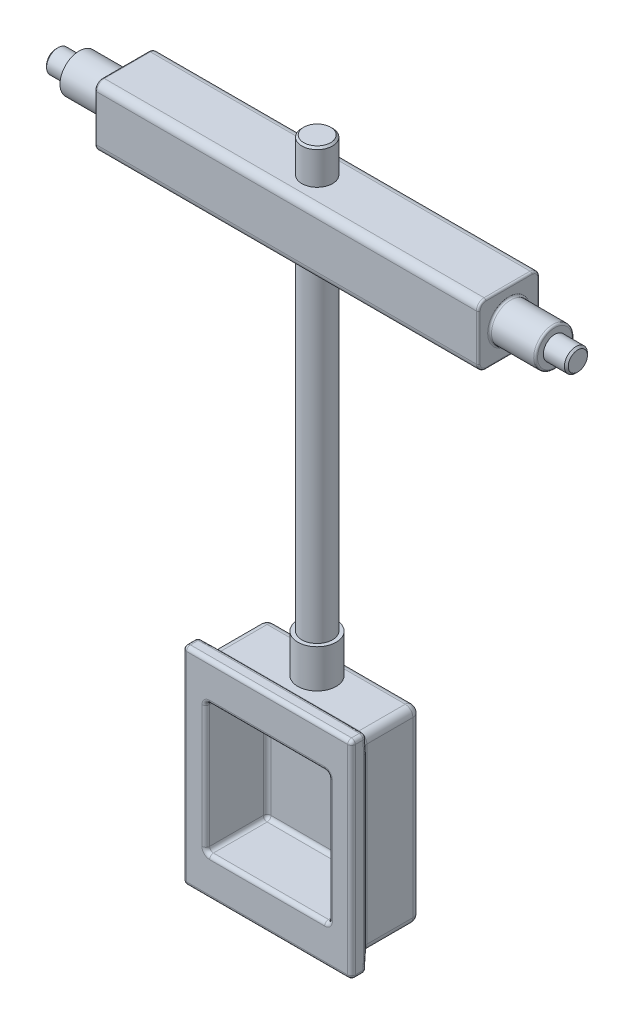
SolidWorks part; units mm, degrees
ref_plane "Front Plane" through (0, 0, 0) normal (0, 0, 1) x (1, 0, 0)
ref_plane "Top Plane" through (0, 0, 0) normal (0, 1, 0) x (1, 0, 0)
ref_plane "Right Plane" through (0, 0, 0) normal (1, 0, 0) x (0, 0, -1)
sketch "Sketch1" plane through (0, 0, 0) normal (0, 0, 1) x (1, 0, 0)
  line L1 (-10, -12.3) -> (10, -12.3)
  line L2 (-10, -12.3) -> (-10, 12.3)
  line L3 (-10, 12.3) -> (10, 12.3)
  line L4 (10, -12.3) -> (10, 12.3)
  line L5 (-10, -12.3) -> (10, 12.3) construction
  line L6 (-10, 12.3) -> (10, -12.3) construction
  line L7 (-8, -8.5) -> (8, -8.5)
  line L8 (-8, -8.5) -> (-8, 8.5)
  line L9 (-8, 8.5) -> (8, 8.5)
  line L10 (8, -8.5) -> (8, 8.5)
  line L11 (-8, -8.5) -> (8, 8.5) construction
  line L12 (-8, 8.5) -> (8, -8.5) construction
  line L13 (-11, -13.5) -> (11, -13.5)
  line L14 (-11, -13.5) -> (-11, 13.5)
  line L15 (-11, 13.5) -> (11, 13.5)
  line L16 (11, -13.5) -> (11, 13.5)
  line L17 (-11, -13.5) -> (11, 13.5) construction
  line L18 (-11, 13.5) -> (11, -13.5) construction
  point P0 (0, 0)
  point P6 (0, 0)
  point P11 (0, 0)
  point P16 (-9.0897, 12.4239)
  dimension "D1" = 17
  dimension "D2" = 16
  dimension "D3" = 22
  dimension "D4" = 27
  dimension "D5" = 1
  dimension "D6" = 1.2
extrude "Boss-Extrude1" add sketch "Sketch1" along normal blind 2 contours L13 L16 L15 L14 L4 L1 L2 L3 | L1 L4 L3 L2 L10 L7 L8 L9 | L7 L10 L9 L8 region at (-9.683, 0, 0) region at (0, 0, 0) region at (-10.6517, 0, 0)
extrude "Boss-Extrude2" add sketch "Sketch1<3>" against normal blind 8 contours L7 L10 L9 L8 | L1 L4 L3 L2 L10 L7 L8 L9 region at (-9.683, 0, 0) region at (0, 0, 0)
sketch "Sketch1<3>" plane through (0, 0, 0) normal (0, 0, 1) x (1, 0, 0) same geometry as "Sketch1"
extrude "Cut-Extrude1" cut sketch "Sketch1<5>" against normal blind 6 and the other way up to next contours L7 L10 L9 L8 region at (0, 0, 0)
sketch "Sketch1<5>" plane through (0, 0, 0) normal (0, 0, 1) x (1, 0, 0) same geometry as "Sketch1"
sketch "Sketch2" plane through (0, 12.3, 0) normal (0, 1, 0) x (1, 0, 0)
  line L0 (-11, -2) -> (11, -2) construction
  circle A1 centre (0, 4.5) radius 2.5
  point P7 (0, 4.5)
  dimension "D2" = 5
  dimension "D1" = 6.5
extrude "Boss-Extrude3" add sketch "Sketch2" along normal blind 5
sketch "Sketch3" plane through (0, 17.3, 0) normal (0, 1, 0) x (1, 0, 0)
  point P0 (0, 4.5)
hole_wizard "M3x0.5 Tapped Hole1" positions "Sketch3" profile "Sketch4" tap size "M3x0.5" standard "ANSI Metric"
sketch "Sketch4" plane through (0, 17.3, -4.5) normal (1, 0, 0) x (0, 0, 1)
  line L0 (0, 0) -> (0, 5)
  line L1 (0, 5) -> (1.25, 4.2489)
  line L2 (1.25, 4.2489) -> (1.25, 0.275)
  line L3 (1.25, 0.275) -> (1.525, 0)
  line L5 (1.525, 0) -> (0, 0)
  line L6 (-1.25, 0.275) -> (-1.525, 0) construction
  line L10 (0, 5) -> (-1.25, 4.2489) construction
  line L11 (0, -6.35) -> (0, 107.95) construction
  dimension "Tap Drill Dia." = 2.5
  dimension "Tap Drill Depth" = 5
  dimension "Near C'Sink Dia." = 3.05
  dimension "Near C'Sink Angle" = 90
  dimension "Drill Angle" = 118
cosmetic thread "Hole Thread1" parameters "D1"=6, "D2"=3
sketch "Sketch6" plane through (0, 0, 0) normal (1, 0, 0) x (0, 0, -1)
  line L0 (4.525, 12.3) -> (4.525, 73.3)
  line L1 (7, 17.3) -> (2, 17.3) construction
  line L2 (4.525, 73.3) -> (6.525, 73.3)
  line L3 (6.525, 73.3) -> (6.525, 17.3)
  line L4 (6.525, 17.3) -> (6.025, 17.3)
  line L5 (6.025, 17.3) -> (6.025, 12.3)
  line L6 (8, 12.3) -> (0, 12.3) construction
  line L7 (6.025, 12.3) -> (4.525, 12.3)
  point P4 (4.5, 12.4479)
  dimension "D1" = 2
  dimension "D2" = 1.5
  dimension "D3" = 61
revolve "Revolve1" add sketch "Sketch6" angle 360 about L0
cosmetic thread "Cosmetic Thread3" parameters "D1"=18, "D2"=3.22
sketch "Sketch7" plane through (0, 0, 0) normal (1, 0, 0) x (0, 0, -1)
  line L0 (6.525, 17.3) -> (6.525, 73.3) construction
  line L1 (1.525, 60.8) -> (7.525, 60.8)
  line L2 (0.525, 61.8) -> (0.525, 67.8)
  line L3 (1.525, 68.8) -> (7.525, 68.8)
  line L4 (8.525, 61.8) -> (8.525, 67.8)
  line L5 (0.525, 60.8) -> (8.525, 68.8) construction
  line L6 (0.525, 68.8) -> (8.525, 60.8) construction
  arc A0 (0.525, 67.8) -> (1.525, 68.8) centre (1.525, 67.8) cw
  arc A1 (1.525, 60.8) -> (0.525, 61.8) centre (1.525, 61.8) cw
  arc A2 (7.525, 60.8) -> (8.525, 61.8) centre (7.525, 61.8) ccw
  arc A3 (7.525, 68.8) -> (8.525, 67.8) centre (7.525, 67.8) cw
  point P0 (4.525, 64.8)
  point P5 (0, 0)
  dimension "D4" = 1
  dimension "D1" = 8
  dimension "D2" = 2
  dimension "D3" = 78.3
extrude "Boss-Extrude4" add sketch "Sketch7" along normal mid plane 50 separate body
sketch "Sketch8" plane through (0, 68.8, 0) normal (0, 1, 0) x (1, 0, 0)
  circle A0 centre (0, 4.525) radius 2
  dimension "D1" = 4
extrude "Cut-Extrude3" cut sketch "Sketch8" against normal up to surface (8 mm away) up to face at (0, 60.8, -4.525)
ref_plane "Plane2" through (0, 0, -4.5) normal (0, 0, 1) x (1, 0, 0)
sketch "Sketch10" plane through (0, 0, -4.5) normal (0, 0, 1) x (1, 0, 0)
  line L0 (54.0916, 64.8) -> (-37.1947, 64.8) construction
  line L2 (25, 67.8) -> (25, 61.8) construction
  line L3 (25, 64.8) -> (25, 67.3)
  line L4 (25, 67.3) -> (31, 67.3)
  line L5 (31, 67.3) -> (31, 66.3)
  line L6 (31, 66.3) -> (34, 66.3)
  line L7 (34, 66.3) -> (34, 64.8)
  line L8 (34, 64.8) -> (25, 64.8)
  line L9 (0, 88.7301) -> (0, 32.2358) construction
  line L10 (-31, 67.3) -> (-31, 66.3)
  line L11 (-31, 66.3) -> (-34, 66.3)
  line L12 (-34, 66.3) -> (-34, 64.8)
  line L13 (-34, 64.8) -> (-25, 64.8)
  line L14 (-25, 64.8) -> (-25, 67.3)
  line L15 (-25, 67.3) -> (-31, 67.3)
  point P6 (25, 64.8)
  dimension "D1" = 6
  dimension "D2" = 3
  dimension "D3" = 1.5
  dimension "D4" = 5
revolve "Revolve2" add sketch "Sketch10" angle 360 about L0
cosmetic thread "Cosmetic Thread1" parameters "D1"=6, "D2"=2.439
cosmetic thread "Cosmetic Thread2" parameters "D1"=6, "D2"=2.439
chamfer "Chamfer1" distance 0.25 angle 45 2 edges at (0, 73.3, -6.525) (0, 12.3, -6.025)
chamfer "Chamfer2" distance 0.25 angle 45 2 edges at (-34, 66.3, -4.5) (34, 66.3, -4.5)
fillet "Fillet1" radius 0.25 19 edges at (-25, 64.8, -0.525) (-25, 61.0929, -0.8179) (-25, 60.8, -4.525) (-25, 61.0929, -8.2321) (-25, 64.8, -8.525) (-25, 68.5071, -8.2321) (-25, 68.8, -4.525) (-25, 68.5071, -0.8179) (-25, 67.3, -4.5) (25, 68.8, -4.525) (25, 68.5071, -8.2321) (25, 64.8, -8.525) (25, 61.0929, -8.2321) (25, 60.8, -4.525) (25, 61.0929, -0.8179) (25, 64.8, -0.525) (25, 68.5071, -0.8179) (25, 67.3, -4.5) (31, 67.3, -4.5)
fillet "Fillet3" radius 1 12 edges at (0, 12.3, 0) (0, -12.3, 0) (-10, -12.3, -4) (-10, 12.3, -4) (-10, 0, 0) (0, 12.3, -8) (-10, 0, -8) (0, -12.3, -8) (10, 12.3, -4) (10, 0, -8) (10, -12.3, -4) (10, 0, 0)
fillet "Fillet4" radius 0.5 28 edges at (0, 8.5, 2) (8, 8.5, -2) (8, 0, 2) (8, -8.5, -2) (0, -8.5, 2) (0, 8.5, -6) (8, 0, -6) (0, -8.5, -6) (-8, 0, 2) (-8, 8.5, -2) (-8, 0, -6) (-8, -8.5, -2) (-11, 0, 0) (-11, 12.4, 0) (-11, 0, 2) (-11, -12.4, 0) (-11, -13.5, 1) (0, -13.5, 2) (0, -13.5, 0) (11, -13.5, 1) (11, 0, 2) (11, 12.4, 0) (11, 0, 0) (11, -12.4, 0) (11, 13.5, 1) (0, 13.5, 2) (-11, 13.5, 1) (0, 13.5, 0)
